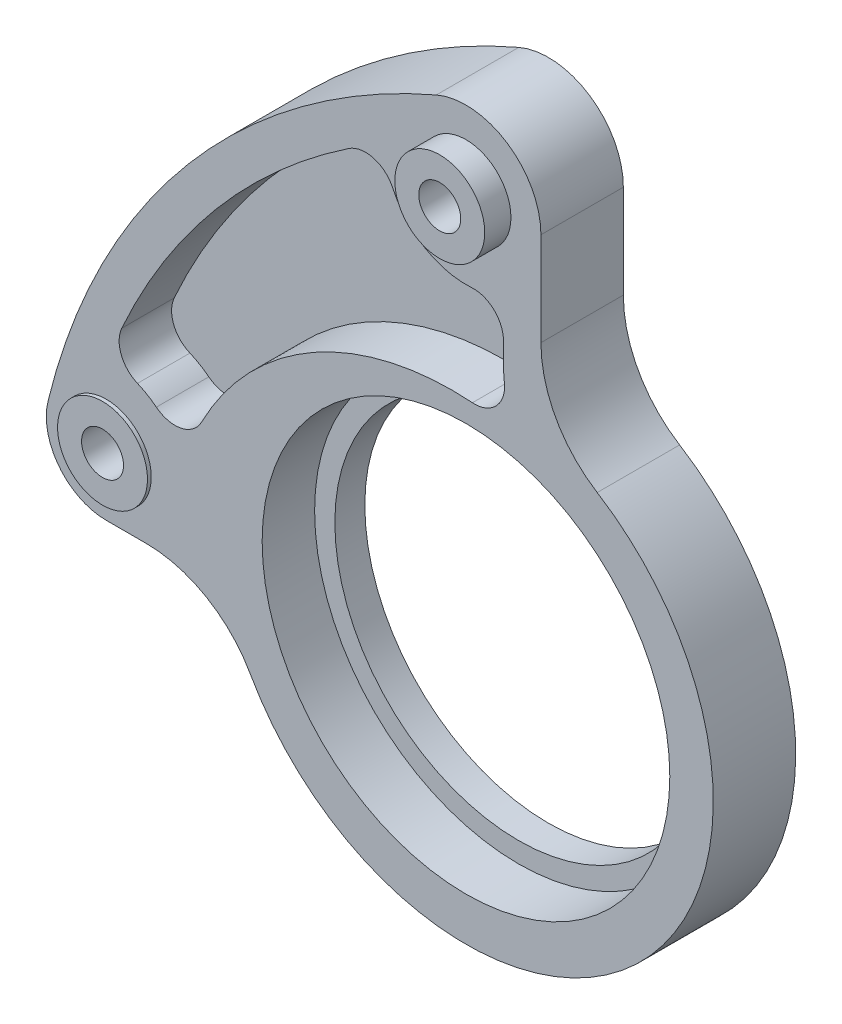
SolidWorks part; units mm, degrees
material "PLA_Shoulder"
ref_plane "Front Plane" through (0, 0, 0) normal (0, 0, 1) x (1, 0, 0)
ref_plane "Top Plane" through (0, 0, 0) normal (0, 1, 0) x (1, 0, 0)
ref_plane "Right Plane" through (0, 0, 0) normal (1, 0, 0) x (0, 0, -1)
ref_plane "Plane1" through (0, 0, 5.5) normal (0, 0, 1) x (1, 0, 0)
sketch "Sketch1" plane through (0, 0, 5.5) normal (0, 0, 1) x (1, 0, 0)
  line L0 (5, 20.7666) -> (5, 27)
  line L1 (-24, -4) -> (-21.36, -4)
  line L2 (-24, 0) -> (0, 0) construction
  line L3 (0, 0) -> (0, 27) construction
  arc A0 (8.7551, 13.9856) -> (5, 20.7666) centre (13, 20.7666) cw
  arc A1 (5, 27) -> (-1.9784, 31.5919) centre (0, 27) ccw
  arc A2 (-1.9784, 31.5919) -> (-27.8856, 0.9498) centre (15.8274, -9.7355) ccw
  arc A3 (-27.8856, 0.9498) -> (-24, -4) centre (-24, 0) ccw
  arc A4 (-21.36, -4) -> (-14.3853, -8.0816) centre (-21.36, -12) cw
  arc A5 (-14.3853, -8.0816) -> (8.7551, 13.9856) centre (0, 0) ccw
  circle A6 centre (0, 0) radius 13.5 construction
  dimension "D1" = 3
  dimension "D2" = 4
  dimension "D3" = 5
  dimension "D4" = 45
  dimension "D5" = 8
  dimension "D8" = 27
  dimension "D6" = 24
  dimension "D7" = 27
extrude "Boss-Extrude1" add sketch "Sketch1" against normal blind 5.5
sketch "Sketch2" plane through (0, 0, 5.5) normal (0, 0, 1) x (1, 0, 0)
  circle A0 centre (0, 27) radius 3
  dimension "D1" = 6
extrude "Boss-Extrude2" add sketch "Sketch2" along normal blind 1.75
sketch "Sketch3" plane through (0, 0, 5.5) normal (0, 0, 1) x (1, 0, 0)
  circle A0 centre (-24, 0) radius 3
  dimension "D1" = 6
extrude "Boss-Extrude3" add sketch "Sketch3" along normal blind 0.25
sketch "Sketch4" plane through (0, 0, 0) normal (0, 0, -1) x (-1, 0, 0)
  circle A0 centre (0, 0) radius 12.25
  dimension "D1" = 24.5
extrude "Cut-Extrude1" cut sketch "Sketch4" against normal through all
sketch "Sketch5" plane through (0, 0, 7.25) normal (0, 0, 1) x (1, 0, 0)
  circle A0 centre (0, 27) radius 1.4
  circle A1 centre (-24, 0) radius 1.4
  dimension "D1" = 2.8
extrude "Cut-Extrude2" cut sketch "Sketch5" against normal through all
sketch "Sketch7" plane through (0, 0, 5.5) normal (0, 0, 1) x (1, 0, 0)
  circle A0 centre (0, 0) radius 13.6
  circle A1 centre (0, 0) radius 13.5 construction
  dimension "D1" = 0.1
  dimension "D2" = 27
extrude "Cut-Extrude4" cut sketch "Sketch7" against normal offset from surface (3.5 mm away) 2 up to face at (-1.4, 27, 0)
sketch "Sketch8" plane through (0, 0, 5.5) normal (0, 0, 1) x (1, 0, 0)
  line L0 (2.5, 18.3644) -> (2.5, 19.6403)
  arc A0 (0.3644, 21.6357) -> (-4.8853, 24.7546) centre (0, 27) cw
  arc A1 (-4.8853, 24.7546) -> (-7.8152, 25.5814) centre (-6.7026, 23.9194) ccw
  arc A2 (-7.8152, 25.5814) -> (-22.9686, 7.6175) centre (15.8274, -9.7355) ccw
  arc A3 (-22.9686, 7.6175) -> (-21.9175, 4.957) centre (-21.1429, 6.8009) ccw
  arc A4 (-21.9175, 4.957) -> (-20.6588, 4.2124) centre (-24, 0) cw
  arc A5 (-20.6588, 4.2124) -> (-17.6384, 4.8627) centre (-19.4159, 5.7794) ccw
  arc A6 (-17.6384, 4.8627) -> (0.4318, 15.0138) centre (-0.9047, -3.7663) cw
  arc A7 (0.4318, 15.0138) -> (2.5619, 17.2256) centre (0.5737, 17.0087) ccw
  arc A8 (2.5619, 17.2256) -> (2.5, 18.3644) centre (13, 18.3644) cw
  arc A9 (2.5, 19.6403) -> (0.3644, 21.6357) centre (0.5, 19.6403) ccw
extrude "Cut-Extrude5" cut sketch "Sketch8" against normal blind 3.5
